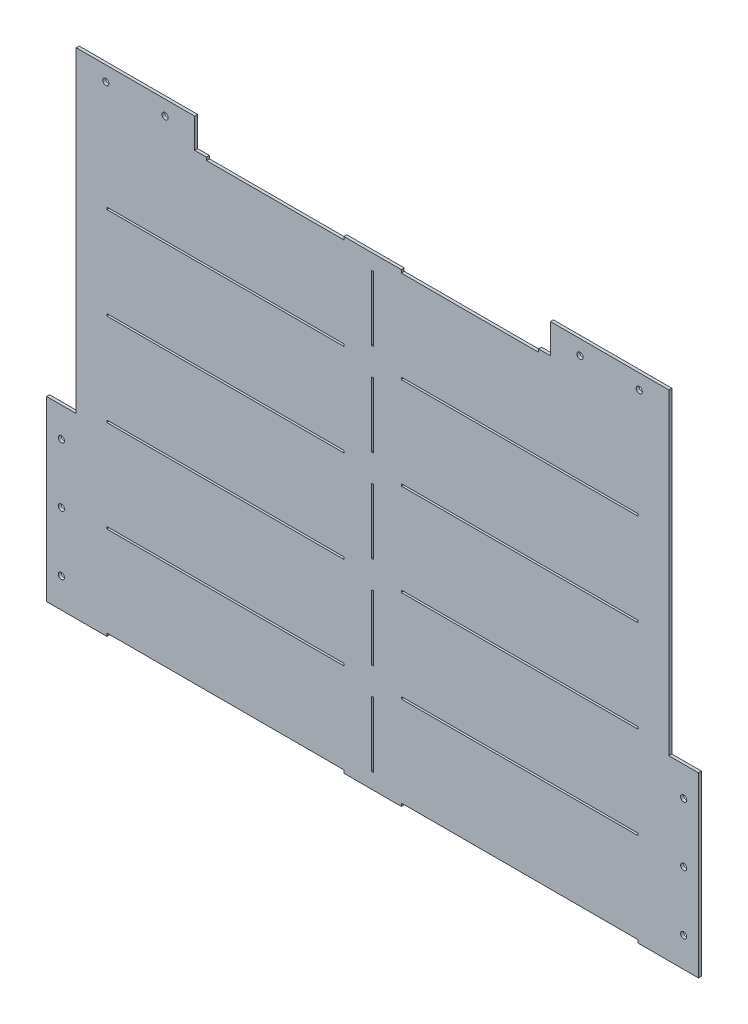
SolidWorks part; units mm, degrees
material "6061-T6 (SS)"
ref_plane "X-Y Datum" through (0, 0, 0) normal (0, 0, 1) x (1, 0, 0)
ref_plane "X-Z Datum" through (0, 0, 0) normal (0, 1, 0) x (1, 0, 0)
ref_plane "Y-Z Datum" through (0, 0, 0) normal (1, 0, 0) x (0, 0, -1)
sketch "Master Sketch" plane through (0, 0, 0) normal (0, 0, 1) x (1, 0, 0)
  line L0 (1.143, 50.5714) -> (314.5028, 50.5714) construction
  line L1 (-317.6778, 249.174) -> (317.6778, 249.174)
  line L2 (-317.6778, 249.174) -> (-317.6778, -249.174)
  line L3 (-317.6778, -249.174) -> (317.6778, -249.174)
  line L4 (317.6778, 249.174) -> (317.6778, -249.174)
  line L5 (-317.6778, 249.174) -> (317.6778, -249.174) construction
  line L6 (-317.6778, -249.174) -> (317.6778, 249.174) construction
  line L7 (-1.143, 249.174) -> (1.143, 249.174) construction
  line L8 (-1.143, 249.174) -> (-1.143, -249.174) construction
  line L9 (-1.143, -249.174) -> (1.143, -249.174) construction
  line L10 (1.143, 249.174) -> (1.143, -249.174) construction
  line L11 (-1.143, 249.174) -> (1.143, -249.174) construction
  line L12 (-1.143, -249.174) -> (1.143, 249.174) construction
  line L13 (1.143, 245.999) -> (314.5028, 245.999) construction
  line L14 (1.143, 245.999) -> (1.143, 149.4282) construction
  line L15 (1.143, 149.4282) -> (314.5028, 149.4282) construction
  line L16 (314.5028, 245.999) -> (314.5028, 149.4282) construction
  line L17 (1.143, 245.999) -> (314.5028, 149.4282) construction
  line L18 (1.143, 149.4282) -> (314.5028, 245.999) construction
  line L19 (1.143, 147.1422) -> (314.5028, 147.1422) construction
  line L20 (314.5028, 147.1422) -> (314.5028, 50.5714) construction
  line L21 (1.143, 147.1422) -> (1.143, 50.5714) construction
  line L22 (1.143, -48.2854) -> (314.5028, -48.2854) construction
  line L23 (1.143, 48.2854) -> (314.5028, 48.2854) construction
  line L24 (314.5028, 48.2854) -> (314.5028, -48.2854) construction
  line L25 (1.143, 48.2854) -> (1.143, -48.2854) construction
  line L26 (1.143, -147.1422) -> (314.5028, -147.1422) construction
  line L27 (1.143, -50.5714) -> (314.5028, -50.5714) construction
  line L28 (314.5028, -50.5714) -> (314.5028, -147.1422) construction
  line L29 (1.143, -50.5714) -> (1.143, -147.1422) construction
  line L30 (1.143, -245.999) -> (314.5028, -245.999) construction
  line L31 (1.143, -149.4282) -> (314.5028, -149.4282) construction
  line L32 (314.5028, -149.4282) -> (314.5028, -245.999) construction
  line L33 (1.143, -149.4282) -> (1.143, -245.999) construction
  line L34 (0, 249.174) -> (0, -249.174) construction
  line L35 (-1.143, -149.4282) -> (-1.143, -245.999) construction
  line L36 (-314.5028, -149.4282) -> (-314.5028, -245.999) construction
  line L37 (-1.143, -149.4282) -> (-314.5028, -149.4282) construction
  line L38 (-1.143, -245.999) -> (-314.5028, -245.999) construction
  line L39 (-1.143, -50.5714) -> (-1.143, -147.1422) construction
  line L40 (-314.5028, -50.5714) -> (-314.5028, -147.1422) construction
  line L41 (-1.143, -50.5714) -> (-314.5028, -50.5714) construction
  line L42 (-1.143, -147.1422) -> (-314.5028, -147.1422) construction
  line L43 (-1.143, 48.2854) -> (-1.143, -48.2854) construction
  line L44 (-314.5028, 48.2854) -> (-314.5028, -48.2854) construction
  line L45 (-1.143, 48.2854) -> (-314.5028, 48.2854) construction
  line L46 (-1.143, -48.2854) -> (-314.5028, -48.2854) construction
  line L47 (-1.143, 147.1422) -> (-1.143, 50.5714) construction
  line L48 (-314.5028, 147.1422) -> (-314.5028, 50.5714) construction
  line L49 (-1.143, 147.1422) -> (-314.5028, 147.1422) construction
  line L50 (-1.143, 149.4282) -> (-314.5028, 245.999) construction
  line L51 (-1.143, 245.999) -> (-314.5028, 149.4282) construction
  line L52 (-314.5028, 245.999) -> (-314.5028, 149.4282) construction
  line L53 (-1.143, 149.4282) -> (-314.5028, 149.4282) construction
  line L54 (-1.143, 245.999) -> (-1.143, 149.4282) construction
  line L55 (-1.143, 245.999) -> (-314.5028, 245.999) construction
  line L56 (-1.143, 249.174) -> (-1.143, -249.174) construction
  line L57 (-1.143, 50.5714) -> (-314.5028, 50.5714) construction
  line L59 (2.413, -152.8699) -> (313.2328, -152.8699) construction
  line L60 (2.413, -152.8699) -> (2.413, -242.5573) construction
  line L61 (2.413, -242.5573) -> (313.2328, -242.5573) construction
  line L62 (313.2328, -152.8699) -> (313.2328, -242.5573) construction
  line L63 (2.413, -152.8699) -> (313.2328, -242.5573) construction
  line L64 (2.413, -242.5573) -> (313.2328, -152.8699) construction
  point P0 (0, 0)
  point P6 (0, 0)
  point P11 (157.8229, 197.7136)
  point P54 (-157.8229, 197.7136)
  point P55 (157.8229, -197.7136)
  point P60 (157.8229, -149.4282)
  point P61 (314.5028, -197.7136)
  point P62 (-314.5028, 98.8568)
  point P63 (-314.5028, 0)
  dimension "D1" = 3.175
  dimension "D2" = 498.348
  dimension "D3" = 2.286
  dimension "D4" = 313.3598
  dimension "D5" = 96.5708
  dimension "D6" = 3.175
  dimension "D7" = 5
  dimension "D8" = 2.286
  dimension "D9" = 89.6874
  dimension "D10" = 310.8198
  dimension "D11" = 98.8568
  dimension "D12" = 635.3556
extrude "Boss-Extrude1" add sketch "Master Sketch" along normal blind 3.175
sketch "Sketch2" plane through (0, 0, 3.175) normal (0, 0, 1) x (1, 0, 0)
  line L0 (0, 317.2302) -> (0, -317.2302) construction
  line L7 (-380.7135, 0) -> (380.7135, 0) construction
  line L9 (-333.5528, -58.674) -> (-333.5528, -249.174) construction
  line L10 (-317.6778, -249.174) -> (-349.4278, -249.174)
  line L11 (-317.6778, -249.174) -> (-317.6778, -58.674)
  line L12 (-317.6778, -58.674) -> (-349.4278, -58.674)
  line L13 (-349.4278, -249.174) -> (-349.4278, -58.674)
  circle A7 centre (-333.5528, -153.924) radius 3 construction
  circle A10 centre (-333.5528, -90.424) radius 3 construction
  circle A11 centre (-333.5528, -153.924) radius 3 construction
  circle A12 centre (-333.5528, -217.424) radius 3 construction
  point P4 (0, 0)
  point P18 (0, 0)
  dimension "D8" = 31.75
  dimension "D10" = 6
  dimension "D9" = 190.5
  dimension "D13" = 63.5
  dimension "D14" = 63.5
  dimension "D11" = 2
  dimension "D12" = 2
extrude "Boss-Extrude2" add sketch "Sketch2" against normal blind 3.175
hole_wizard "M6 Clearance Hole1" positions "Sketch3" profile "Sketch4" hole size "M6" standard "ANSI Metric" end condition through all
sketch "Sketch3" plane through (0, 0, 3.175) normal (0, 0, 1) x (1, 0, 0)
  point P34 (-333.5528, -90.424)
  point P37 (-333.5528, -153.924)
  point P40 (-333.5528, -217.424)
sketch "Sketch4" plane through (-333.5528, -90.424, 3.175) normal (1, 0, 0) x (0, -1, 0)
  line L0 (0, 0) -> (0, 3.175)
  line L1 (0, 3.175) -> (3.3, 3.175)
  line L2 (3.3, 3.175) -> (3.3, 0)
  line L5 (3.3, 0) -> (0, 0)
  line L11 (0, -6.35) -> (0, 107.95) construction
  dimension "Thru Hole Dia." = 6.6
  dimension "Thru Hole Depth" = 3.175
mirror "Mirror1" about plane through (0, 0, 0) normal (1, 0, 0) of "Boss-Extrude2", "M6 Clearance Hole1"
sketch "Sketch5" plane through (0, 0, 3.175) normal (0, 0, 1) x (1, 0, 0)
  line L5 (-1.143, 232.6386) -> (1.143, 232.6386)
  line L6 (-1.143, 232.6386) -> (-1.143, 162.7886)
  line L7 (-1.143, 162.7886) -> (1.143, 162.7886)
  line L8 (1.143, 232.6386) -> (1.143, 162.7886)
  line L9 (-157.8229, 197.7136) -> (157.8229, 197.7136) construction
  line L10 (-1.143, 232.6386) -> (1.143, 162.7886) construction
  line L11 (-1.143, 162.7886) -> (1.143, 232.6386) construction
  point P0 (0, 0)
  point P1 (0, 197.7136)
  dimension "D1" = 2.286
  dimension "D2" = 69.85
extrude "Cut-Extrude1" cut sketch "Sketch5" against normal through all
pattern_linear "LPattern1" count 5 spacing 98.8568 along (0, -1, 0) of "Cut-Extrude1"
sketch "Sketch7" plane through (0, 0, 3.175) normal (0, 0, 1) x (1, 0, 0)
  line L0 (-157.8229, 149.4282) -> (-157.8229, 147.1422) construction
  line L1 (-1.143, 149.4282) -> (-314.5028, 149.4282) construction
  line L2 (-1.143, 147.1422) -> (-314.5028, 147.1422) construction
  line L3 (-157.8229, 50.5714) -> (-157.8229, 48.2854) construction
  line L4 (-284.8229, 149.4282) -> (-30.8229, 149.4282)
  line L5 (-284.8229, 149.4282) -> (-284.8229, 147.1422)
  line L6 (-284.8229, 147.1422) -> (-30.8229, 147.1422)
  line L7 (-30.8229, 149.4282) -> (-30.8229, 147.1422)
  line L8 (-284.8229, 149.4282) -> (-30.8229, 147.1422) construction
  line L9 (-284.8229, 147.1422) -> (-30.8229, 149.4282) construction
  line L10 (-1.143, 50.5714) -> (-314.5028, 50.5714) construction
  line L11 (-1.143, 48.2854) -> (-314.5028, 48.2854) construction
  point P6 (-157.8229, 148.2852)
  dimension "D1" = 2.286
  dimension "D2" = 254
extrude "Cut-Extrude3" cut sketch "Sketch7" against normal through all
pattern_linear "LPattern2" count 4 spacing 98.8568 along (0, -1, 0) of "Cut-Extrude3"
mirror "Mirror4" about plane through (0, 0, 0) normal (1, 0, 0) of "LPattern2", "Cut-Extrude3"
sketch "Sketch10" plane through (0, 0, 3.175) normal (0, 0, 1) x (1, 0, 0)
  line L8 (-317.6778, 265.049) -> (-190.6778, 265.049) construction
  line L9 (-317.6778, 249.174) -> (-190.6778, 249.174)
  line L10 (-317.6778, 249.174) -> (-317.6778, 280.924)
  line L11 (-317.6778, 280.924) -> (-190.6778, 280.924)
  line L12 (-190.6778, 249.174) -> (-190.6778, 280.924)
  line L13 (-254.1778, 280.924) -> (-254.1778, 249.174) construction
  line L14 (-254.1778, 265.049) -> (-317.6778, 265.049) construction
  line L15 (-317.6778, 265.049) -> (-285.9278, 265.049) construction
  line L16 (-285.9278, 265.049) -> (-285.9278, 273.0891) construction
  circle A2 centre (-285.9278, 265.049) radius 3 construction
  circle A3 centre (-222.4278, 265.049) radius 3 construction
  dimension "D6" = 6
  dimension "D1" = 63.5
  dimension "D4" = 31.75
  dimension "D5" = 127
extrude "Boss-Extrude3" add sketch "Sketch10" against normal blind 3.175
hole_wizard "M6 Clearance Hole2" positions "Sketch11" profile "Sketch12" hole size "M6" standard "ANSI Metric" end condition through all
sketch "Sketch11" plane through (0, 0, 3.175) normal (0, 0, 1) x (1, 0, 0)
  point P7 (-285.9278, 265.049)
  point P10 (-222.4278, 265.049)
sketch "Sketch12" plane through (-285.9278, 265.049, 3.175) normal (1, 0, 0) x (0, -1, 0)
  line L0 (0, 0) -> (0, 3.175)
  line L1 (0, 3.175) -> (3.3, 3.175)
  line L2 (3.3, 3.175) -> (3.3, 0)
  line L5 (3.3, 0) -> (0, 0)
  line L11 (0, -6.35) -> (0, 107.95) construction
  dimension "Thru Hole Dia." = 6.6
  dimension "Thru Hole Depth" = 3.175
mirror "Mirror6" about plane through (0, 0, 0) normal (1, 0, 0) of "M6 Clearance Hole2", "Boss-Extrude3"
sketch "Sketch6" plane through (0, 0, 3.175) normal (0, 0, 1) x (1, 0, 0)
  line L0 (-157.8229, 245.999) -> (-157.8229, 249.174) construction
  line L1 (-1.143, 245.999) -> (-314.5028, 245.999) construction
  line L2 (-317.6778, 249.174) -> (317.6778, 249.174) construction
  line L3 (0, -78.309) -> (0, 78.309) construction
  line L4 (-284.8229, 249.174) -> (-30.8229, 249.174)
  line L5 (-284.8229, 249.174) -> (-284.8229, 245.999)
  line L6 (-284.8229, 245.999) -> (-30.8229, 245.999)
  line L7 (-30.8229, 249.174) -> (-30.8229, 245.999)
  line L8 (-284.8229, 249.174) -> (-30.8229, 245.999) construction
  line L9 (-284.8229, 245.999) -> (-30.8229, 249.174) construction
  line L10 (30.8229, 249.174) -> (30.8229, 245.999)
  line L11 (284.8229, 249.174) -> (30.8229, 249.174)
  line L12 (284.8229, 245.999) -> (30.8229, 245.999)
  line L13 (284.8229, 249.174) -> (284.8229, 245.999)
  line L14 (1.7463, 0) -> (-1.7463, 0) construction
  line L15 (-284.8229, -245.999) -> (-30.8229, -249.174) construction
  line L16 (-284.8229, -249.174) -> (-30.8229, -245.999) construction
  line L17 (-157.8229, -245.999) -> (-157.8229, -249.174) construction
  line L18 (284.8229, -249.174) -> (284.8229, -245.999)
  line L19 (284.8229, -245.999) -> (30.8229, -245.999)
  line L20 (284.8229, -249.174) -> (30.8229, -249.174)
  line L21 (30.8229, -249.174) -> (30.8229, -245.999)
  line L22 (-30.8229, -249.174) -> (-30.8229, -245.999)
  line L23 (-284.8229, -245.999) -> (-30.8229, -245.999)
  line L24 (-284.8229, -249.174) -> (-284.8229, -245.999)
  line L25 (-284.8229, -249.174) -> (-30.8229, -249.174)
  line L26 (-177.9778, 245.999) -> (-177.9778, 249.174)
  line L27 (-190.6778, 249.174) -> (-190.6778, 280.924) construction
  line L28 (177.9778, 245.999) -> (177.9778, 249.174)
  point P6 (-157.8229, 247.5865)
  point P29 (-157.8229, -247.5865)
  dimension "D1" = 3.175
  dimension "D2" = 254
  dimension "D3" = 12.7
extrude "Cut-Extrude2" cut sketch "Sketch6" against normal through all contours L24 L22 L23 | L21 L18 L19 | L26 L6 L7 L4 | L12 L28 L11 L10 region at (-104.4004, 247.5865, 3.175) region at (104.4004, 247.5865, 3.175) region at (157.8229, -247.5865, 3.175) region at (-157.8229, -247.5865, 3.175)
